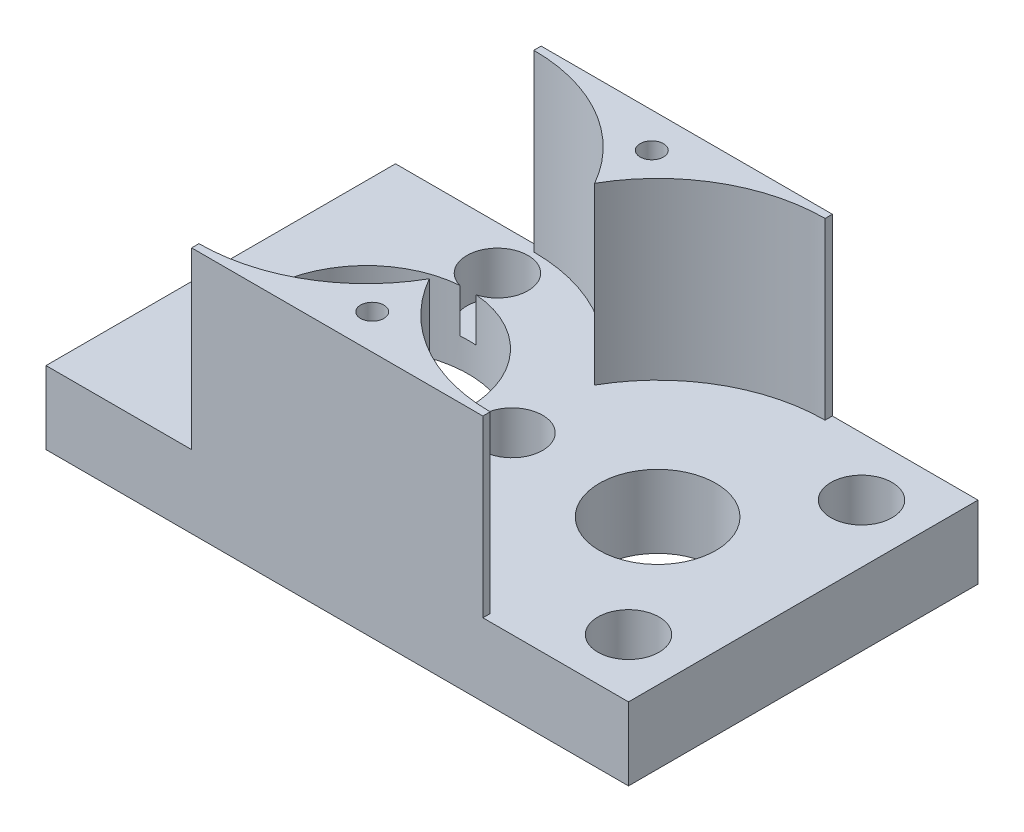
SolidWorks part; units mm, degrees
ref_plane "前视基准面" through (0, 0, 0) normal (0, 0, 1) x (1, 0, 0)
ref_plane "上视基准面" through (0, 0, 0) normal (0, 1, 0) x (1, 0, 0)
ref_plane "右视基准面" through (0, 0, 0) normal (1, 0, 0) x (0, 0, -1)
other "Configuration Table"
sketch "草图1" plane through (0, 0, 0) normal (0, 1, 0) x (1, 0, 0)
  line L5 (0, 0) -> (20, 0)
  line L6 (0, 0) -> (0, 12)
  line L11 (0, 12) -> (20, 12)
  line L12 (20, 0) -> (20, 12)
  dimension "D1" = 20
  dimension "D2" = 12
extrude "凸台-拉伸1" add sketch "草图1" along normal blind 2.5
sketch "草图2" plane through (0, 2.5, 0) normal (0, 1, 0) x (1, 0, 0)
  line L0 (20, 12) -> (0, 12) construction
  line L1 (0, 12) -> (0, 0) construction
  line L2 (20, 0) -> (20, 12) construction
  circle A0 centre (15, 6) radius 2
  circle A1 centre (5, 6) radius 3.5
  dimension "D1" = 4
  dimension "D2" = 7
  dimension "D3" = 6
  dimension "D4" = 5
  dimension "D5" = 5
extrude "切除-拉伸1" cut sketch "草图2" against normal through all
sketch "草图3" plane through (0, 0, 0) normal (0, -1, 0) x (1, 0, 0)
  circle A0 centre (18, -2) radius 0.5
  circle A1 centre (18, -10) radius 0.5
  circle A2 centre (10, -6) radius 0.5
  circle A3 centre (5, -1.5) radius 0.5
  circle A4 centre (5, -10.5) radius 0.5
  circle A5 centre (5, -10.5) radius 1.05
  circle A6 centre (5, -1.5) radius 1.05
  circle A7 centre (18, -2) radius 1.05
  circle A8 centre (10, -6) radius 1.05
  circle A9 centre (18, -10) radius 1.05
  dimension "D1" = 1
  dimension "D2" = 2.1
extrude "切除-拉伸3" cut sketch "草图3" against normal through all contours A3 | A4 | A2 | A0 | A1
extrude "切除-拉伸6" cut sketch "草图3<4>" along normal offset from surface (1.5 mm away) 1 from surface up to face at (18, 0, -10.5) starting at face at (18, 2.5, -10.5)
sketch "草图3<4>" plane through (0, 0, 0) normal (0, -1, 0) x (1, 0, 0) same geometry as "草图3"
sketch "草图4" plane through (0, 2.5, 0) normal (0, 1, 0) x (1, 0, 0)
  line L0 (20, 12) -> (0, 12) construction
  line L1 (15, 12) -> (5, 12)
  line L2 (15, 12) -> (15, 0)
  line L3 (15, 0) -> (5, 0)
  line L4 (5, 12) -> (5, 0)
  line L5 (0, 0) -> (20, 0) construction
  circle A0 centre (15, 6) radius 5.75
  circle A1 centre (5, 6) radius 5.75
  line M9 (0, 0) -> (20, 0)
  line M11 (20, 12) -> (0, 12)
  dimension "D1" = 11.5
extrude "凸台-拉伸2" add sketch "草图4" along normal blind 6 contours A1 A0 L2 L4 M11 | A1 L4 L2 A0 M9 region at (10, 2.5, -11.1492) region at (10, 2.5, -0.8508)
sketch "草图5" plane through (0, 8.5, 0) normal (0, 1, 0) x (1, 0, 0)
  line L0 (15, 12) -> (5, 12) construction
  line L1 (5, 0) -> (15, 0) construction
  circle A0 centre (10, 1.2) radius 0.4
  circle A1 centre (10, 10.8) radius 0.4
  dimension "D3" = 0.8
  dimension "D1" = 1.2
  dimension "D2" = 1.2
extrude "切除-拉伸7" cut sketch "草图5" against normal blind 2
